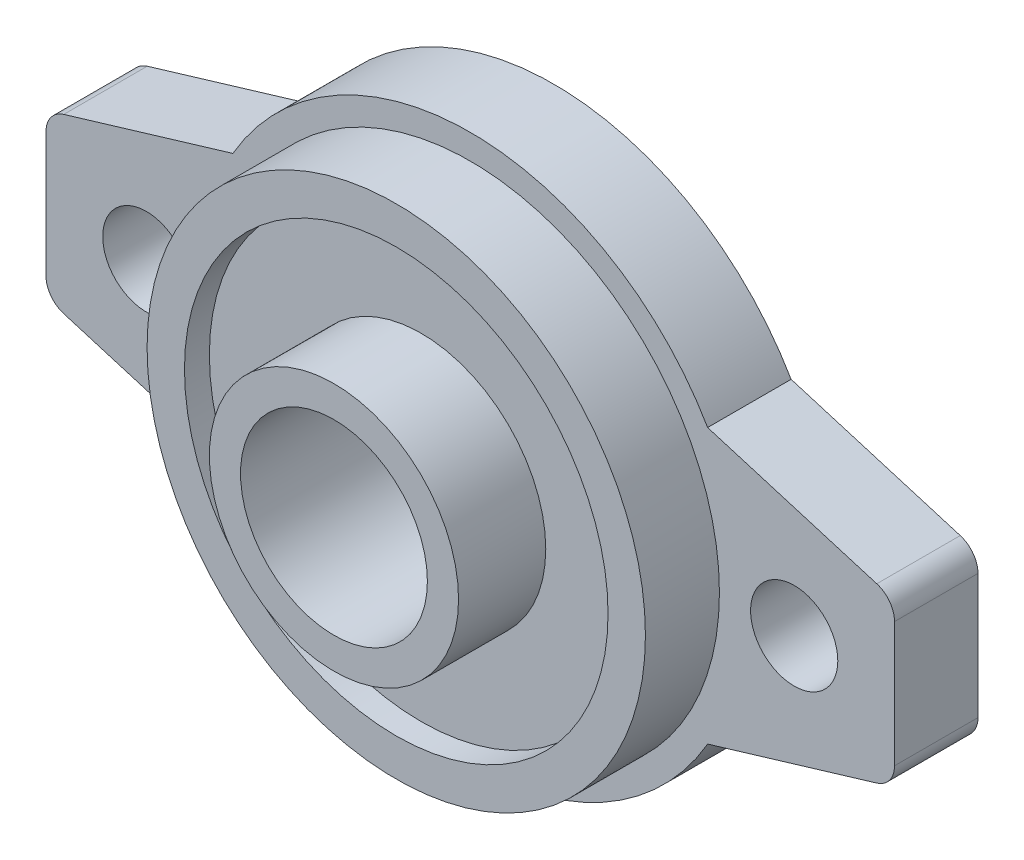
SolidWorks part; units mm, degrees
ref_plane "정면" through (0, 0, 0) normal (0, 0, 1) x (1, 0, 0)
ref_plane "윗면" through (0, 0, 0) normal (0, 1, 0) x (1, 0, 0)
ref_plane "우측면" through (0, 0, 0) normal (1, 0, 0) x (0, 0, -1)
sketch "스케치1" plane through (0, 0, 0) normal (0, 0, 1) x (1, 0, 0)
  line L0 (19.0526, 11) -> (34.0526, 6.5)
  line L4 (34.0526, 6.5) -> (34.0526, -6.5)
  line L5 (34.0526, -6.5) -> (19.0526, -11)
  line L6 (38.0288, 0) -> (-37.9012, 0) construction
  line L7 (0, 30.3127) -> (0, -31.0312) construction
  line L8 (-34.0526, -6.5) -> (-19.0526, -11)
  line L9 (-34.0526, 6.5) -> (-34.0526, -6.5)
  line L10 (-19.0526, 11) -> (-34.0526, 6.5)
  circle A0 centre (0, 0) radius 7.5
  circle A1 centre (0, 0) radius 20
  circle A2 centre (0, 0) radius 10
  arc A3 (19.0526, 11) -> (-19.0526, 11) centre (0, 0) ccw
  circle A4 centre (26, 0) radius 3.5
  circle A5 centre (0, 0) radius 22 construction
  circle A6 centre (-26, 0) radius 3.5
  circle A7 centre (0, 0) radius 17
  arc A8 (-19.0526, -11) -> (19.0526, -11) centre (0, 0) ccw
  dimension "D1" = 15
  dimension "D2" = 40
  dimension "D3" = 20
  dimension "D8" = 7
  dimension "D5" = 22
  dimension "D6" = 13
  dimension "D7" = 15
  dimension "D9" = 52
  dimension "D4" = 2
  dimension "D10" = 3
extrude "보스-돌출1" add sketch "스케치1" along normal blind 6.7 contours L8 A8 L5 L4 L0 A3 L10 L9 A6 A4 A1 | A1 A2 | A2 A0 | A7 region at (26.3196, 7.9734, 0) region at (-19.4343, 0, 0) region at (-9.7172, 0, 0)
extrude "보스-돌출2" add sketch "스케치1<4>" along normal blind 12.64 contours A1 A2 region at (-19.4343, 0, 0)
sketch "스케치1<4>" plane through (0, 0, 0) normal (0, 0, 1) x (1, 0, 0) same geometry as "스케치1"
extrude "보스-돌출3" add sketch "스케치1<5>" along normal offset from surface (10.64 mm away) 2 contours A7 A2 region at (-16.5192, 0, 0) up to face at (17, 0, 12.64)
sketch "스케치1<5>" plane through (0, 0, 0) normal (0, 0, 1) x (1, 0, 0) same geometry as "스케치1"
extrude "보스-돌출4" add sketch "스케치1<6>" along normal offset from surface (17.64 mm away) 7 contours A2 A0 region at (-9.7172, 0, 0) up to face at (10, 0, 10.64) offset beyond the face yes
sketch "스케치1<6>" plane through (0, 0, 0) normal (0, 0, 1) x (1, 0, 0) same geometry as "스케치1"
fillet "필렛1" radius 2 4 edges at (-34.0526, -6.5, 3.35) (-34.0526, 6.5, 3.35) (34.0526, -6.5, 3.35) (34.0526, 6.5, 3.35)
